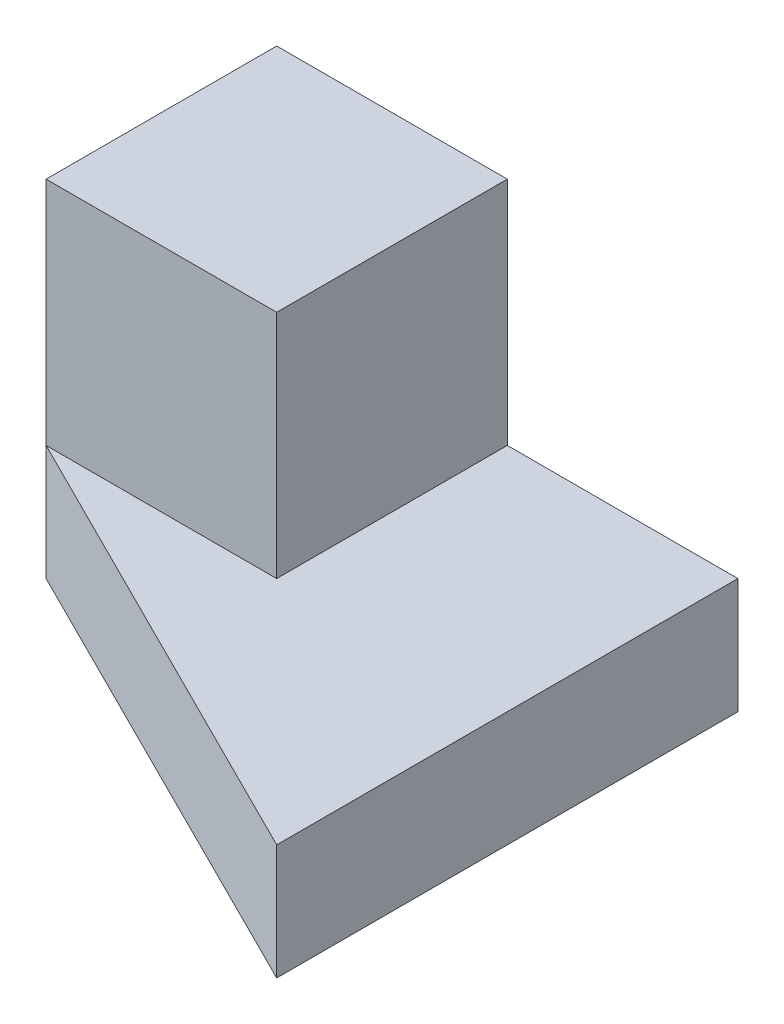
SolidWorks part; units mm, degrees
ref_plane "前基準面" through (0, 0, 0) normal (0, 0, 1) x (1, 0, 0)
ref_plane "上基準面" through (0, 0, 0) normal (0, 1, 0) x (1, 0, 0)
ref_plane "右基準面" through (0, 0, 0) normal (1, 0, 0) x (0, 0, -1)
sketch "草圖1" plane through (0, 0, 0) normal (0, 1, 0) x (1, 0, 0)
  line L0 (0, 20) -> (40, 20)
  line L1 (0, 0) -> (20, 0)
  line L2 (0, 0) -> (0, 20)
  line L3 (0, 20) -> (20, 20)
  line L4 (20, 0) -> (20, 20)
  line L5 (40, 20) -> (40, -20)
  line L6 (40, -20) -> (0, 0)
  dimension "D1" = 40
  dimension "D2" = 40
  dimension "D3" = 20
  dimension "D4" = 20
extrude "填料-伸長4" add sketch "草圖1" against normal blind 10 contours L1 L4 L0 L2 | L6 L5 L0 L4 L1 region at (10, 0, -10) region at (28.3333, 0, -1.6667)
extrude "填料-伸長5" add sketch "草圖1<6>" along normal blind 20 contours L1 L4 L0 L2 region at (10, 0, -10)
sketch "草圖1<6>" plane through (0, 0, 0) normal (0, 1, 0) x (1, 0, 0) same geometry as "草圖1"
